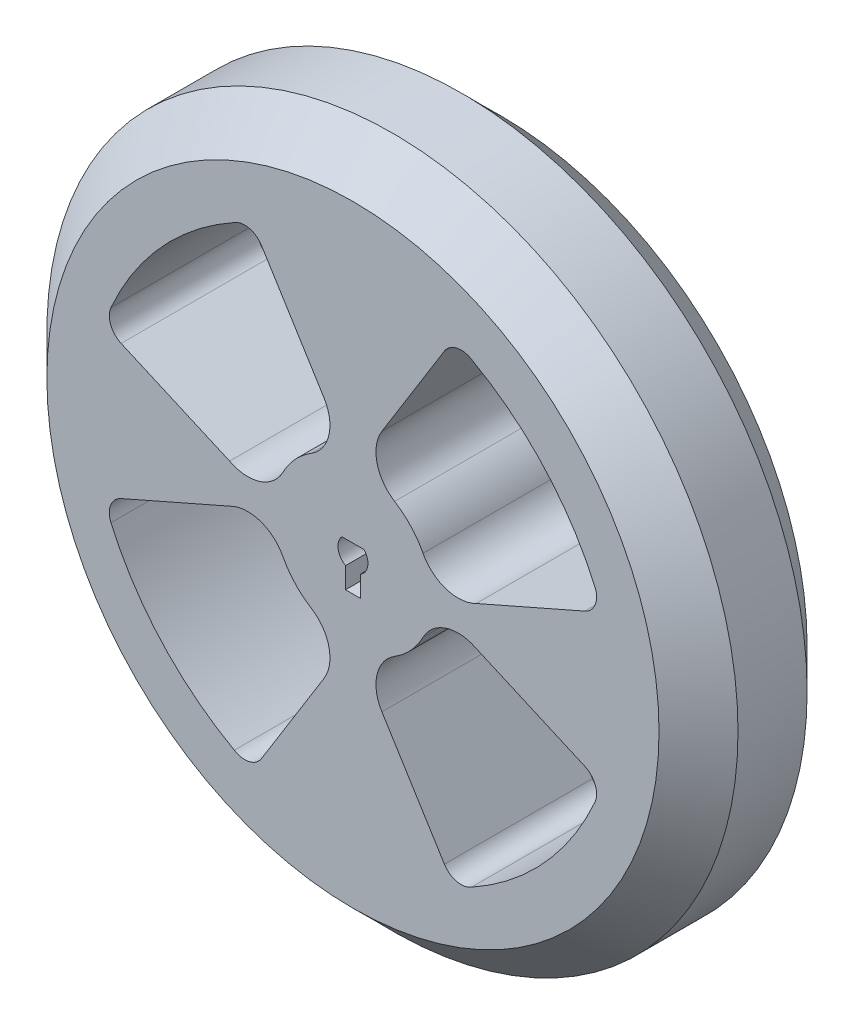
SolidWorks part; units mm, degrees
ref_plane "Front Plane" through (0, 0, 0) normal (0, 0, 1) x (1, 0, 0)
ref_plane "Top Plane" through (0, 0, 0) normal (0, 1, 0) x (1, 0, 0)
ref_plane "Right Plane" through (0, 0, 0) normal (1, 0, 0) x (0, 0, -1)
sketch "Sketch1" plane through (0, 0, 0) normal (0, 0, 1) x (1, 0, 0)
  circle A0 centre (0, 0) radius 35
  dimension "D1" = 70
extrude "Boss-Extrude1" add sketch "Sketch1" along normal blind 15
sketch "Sketch2" plane through (0, 0, 15) normal (0, 0, 1) x (1, 0, 0)
  line L0 (0, 8) -> (0, -8) construction
  line L1 (1.12, 1.025) -> (-1.12, 1.025)
  line L2 (0.75, -1.32) -> (0.75, -3.4416)
  line L3 (0.75, -3.4416) -> (-0.75, -3.4416)
  line L4 (-0.75, -1.32) -> (-0.75, -3.4416)
  arc A1 (1.12, 1.025) -> (0.75, -1.32) centre (0, 0) cw
  arc A2 (-1.12, 1.025) -> (-0.75, -1.32) centre (0, 0) ccw
  point P11 (0, -3.4416)
  point P13 (0, 1.025)
  dimension "D1" = 0.75
  dimension "D2" = 2.24
sketch "Sketch3" plane through (0, 0, 15) normal (0, 0, 1) x (1, 0, 0)
  line L0 (0, 0) -> (35, 0) construction
  line L1 (35, 0) -> (-30, 0) construction
  line L2 (-2.9315, 12.3047) -> (-9.2613, 22.4995)
  line L3 (-12.4935, 1.9782) -> (-23.4804, 6.804)
  line L4 (-2.9315, -12.3047) -> (-9.2613, -22.4995)
  line L5 (-12.4935, -1.9782) -> (-23.4804, -6.804)
  line L6 (0, 0) -> (0, -31.0217) construction
  line L7 (0, -31.0217) -> (0, 34.4427) construction
  line L8 (2.9315, -12.3047) -> (9.2613, -22.4995)
  line L9 (12.4935, -1.9782) -> (23.4804, -6.804)
  line L10 (2.9315, 12.3047) -> (9.2613, 22.4995)
  line L11 (12.4935, 1.9782) -> (23.4804, 6.804)
  circle A0 centre (0, 0) radius 35 construction
  arc A1 (-23.4804, -6.804) -> (-24.5072, -9.4394) centre (-22.6761, -8.6351) ccw
  arc A3 (-9.2613, -22.4995) -> (-12.0154, -23.1437) centre (-10.9605, -21.4445) cw
  arc A4 (-4.2199, -6.7965) -> (-2.9315, -12.3047) centre (-6.3298, -10.1948) cw
  arc A5 (-7.1005, -3.6856) -> (-12.4935, -1.9782) centre (-10.6507, -5.5284) ccw
  arc A6 (-24.5072, -9.4394) -> (-12.0154, -23.1437) centre (2.0557, 2.2279) ccw
  arc A7 (-9.2613, 22.4995) -> (-12.0154, 23.1437) centre (-10.9605, 21.4445) ccw
  arc A8 (-4.2199, 6.7965) -> (-2.9315, 12.3047) centre (-6.3298, 10.1948) ccw
  arc A9 (-7.1005, 3.6856) -> (-12.4935, 1.9782) centre (-10.6507, 5.5284) cw
  arc A10 (-23.4804, 6.804) -> (-24.5072, 9.4394) centre (-22.6761, 8.6351) cw
  arc A11 (-24.5072, 9.4394) -> (-12.0154, 23.1437) centre (2.0557, -2.2279) cw
  arc A12 (7.1005, -3.6856) -> (12.4935, -1.9782) centre (10.6507, -5.5284) cw
  arc A13 (4.2199, -6.7965) -> (2.9315, -12.3047) centre (6.3298, -10.1948) ccw
  arc A14 (9.2613, -22.4995) -> (12.0154, -23.1437) centre (10.9605, -21.4445) ccw
  arc A15 (24.5072, -9.4394) -> (12.0154, -23.1437) centre (-2.0557, 2.2279) cw
  arc A16 (23.4804, -6.804) -> (24.5072, -9.4394) centre (22.6761, -8.6351) cw
  arc A17 (9.2613, 22.4995) -> (12.0154, 23.1437) centre (10.9605, 21.4445) cw
  arc A18 (4.2199, 6.7965) -> (2.9315, 12.3047) centre (6.3298, 10.1948) cw
  arc A19 (7.1005, 3.6856) -> (12.4935, 1.9782) centre (10.6507, 5.5284) ccw
  arc A20 (23.4804, 6.804) -> (24.5072, 9.4394) centre (22.6761, 8.6351) ccw
  arc A21 (24.5072, 9.4394) -> (12.0154, 23.1437) centre (-2.0557, -2.2279) ccw
  arc A22 (-7.1005, 3.6856) -> (-4.2199, 6.7965) centre (0, 0) cw
  arc A23 (4.2199, 6.7965) -> (7.1005, 3.6856) centre (0, 0) cw
  arc A24 (-7.1005, -3.6856) -> (-4.2199, -6.7965) centre (0, 0) ccw
  arc A25 (4.2199, -6.7965) -> (7.1005, -3.6856) centre (0, 0) ccw
  dimension "D1" = 4
  dimension "D2" = 4
  dimension "D6" = 12
extrude "Cut-Extrude1" cut sketch "Sketch3" against normal blind 15
extrude "Cut-Extrude3" cut sketch "Sketch2" against normal blind 15
fillet "Chamfer1" radius 4 1 edges at (35, 0, 0) type face fillet profile chamfer first side face at (35, 0, 15) second side face at (0, -1.2752, 0)
fillet "Chamfer2" radius 4 1 edges at (35, 0, 15) type face fillet profile chamfer first side face at (35, 0, 4) second side face at (0, -1.2752, 15)
